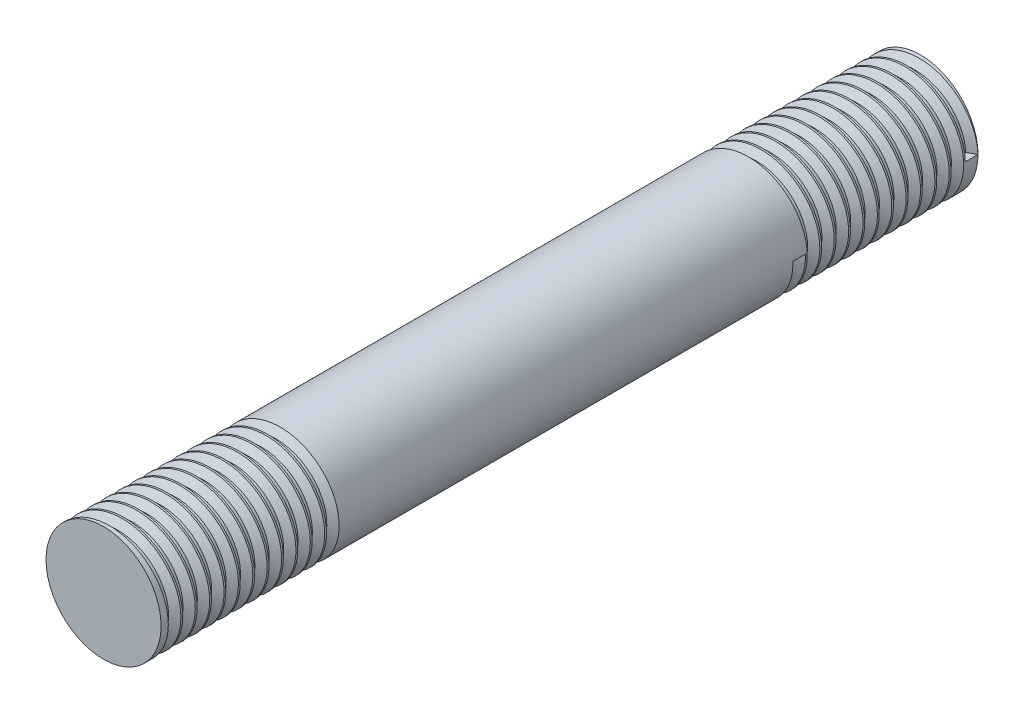
SolidWorks part; units mm, degrees
ref_plane "Płaszczyzna przednia" through (0, 0, 0) normal (0, 0, 1) x (1, 0, 0)
ref_plane "Płaszczyzna górna" through (0, 0, 0) normal (0, 1, 0) x (1, 0, 0)
ref_plane "Płaszczyzna prawa" through (0, 0, 0) normal (1, 0, 0) x (0, 0, -1)
sketch "Szkic1" plane through (0, 0, 0) normal (0, 0, 1) x (1, 0, 0)
  circle A0 centre (0, 0) radius 10
  dimension "D1" = 20
extrude "Dodanie-wyciągnięcie1" add sketch "Szkic1" along normal blind 142
thread "Gwint1" pitch 2.5 method cut profile "Profil gwintu1" start angle 0, offset 0, length 30, pitch 2.5, diameter 20
ref_plane "Płaszczyzna1" through (10, 0, 0) normal (0, -1, 0) x (1, 0, 0)
sketch "Profil gwintu1" plane through (10, 0, 0) normal (0, -1, 0) x (1, 0, 0)
  line L0 (0, 0) -> (0, 2.5) construction
  line L11 (0, 0) -> (0, 2.1875)
  line L12 (0, 2.1875) -> (-1.3532, 1.4062)
  line L13 (-1.3532, 1.4062) -> (-1.3532, 0.7812)
  line L15 (-1.3532, 0.7812) -> (0, 0)
  line L17 (-1.3532, 1.0937) -> (0, 1.0937) construction
  point P2 (0, 0)
  dimension "Pitch" = 2.5
  dimension "Profile_Angle" = 60
  dimension "Profile_Land" = 0.625
  dimension "Profile_Height" = 1.3532
thread "Gwint2" pitch 2.5 method cut profile "Profil gwintu2" start angle 0, offset 0, length 30, pitch 2.5, diameter 20
ref_plane "Płaszczyzna2" through (-10, 0, 142) normal (0, -1, 0) x (-1, 0, 0)
sketch "Profil gwintu2" plane through (-10, 0, 142) normal (0, -1, 0) x (-1, 0, 0)
  line L0 (0, 0) -> (0, 2.5) construction
  line L11 (0, 0) -> (0, 2.1875)
  line L12 (0, 2.1875) -> (-1.3532, 1.4062)
  line L13 (-1.3532, 1.4062) -> (-1.3532, 0.7812)
  line L15 (-1.3532, 0.7812) -> (0, 0)
  line L17 (-1.3532, 1.0937) -> (0, 1.0937) construction
  point P2 (0, 0)
  dimension "Pitch" = 2.5
  dimension "Profile_Angle" = 60
  dimension "Profile_Land" = 0.625
  dimension "Profile_Height" = 1.3532
